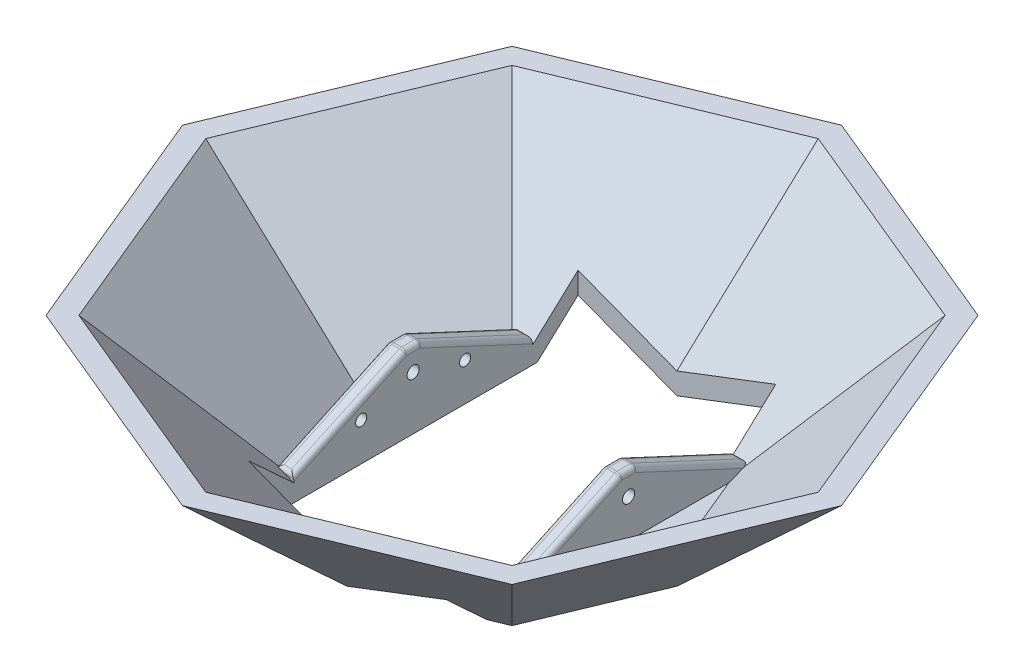
SolidWorks part; units mm, degrees
ref_plane "Ebene vorne" through (0, 0, 0) normal (0, 0, 1) x (1, 0, 0)
ref_plane "Ebene oben" through (0, 0, 0) normal (0, 1, 0) x (1, 0, 0)
ref_plane "Ebene rechts" through (0, 0, 0) normal (1, 0, 0) x (0, 0, -1)
sketch "Skizze1" plane through (0, 0, 0) normal (0, 1, 0) x (1, 0, 0)
  line L1 (-55, 0) -> (55, 0) construction
  line L5 (45.9619, -45.9619) -> (65, 0)
  line L6 (-65, 0) -> (65, 0) construction
  line L7 (0, -55) -> (0, 55) construction
  line L8 (0, 65) -> (0, -65) construction
  line L9 (0, -65) -> (45.9619, -45.9619)
  line L10 (45.9619, 45.9619) -> (-45.9619, -45.9619) construction
  line L11 (45.9619, -45.9619) -> (-45.9619, 45.9619) construction
  line L12 (-45.9619, -45.9619) -> (0, -65)
  line L15 (-65, 0) -> (-45.9619, -45.9619)
  line L16 (-45.9619, 45.9619) -> (-65, 0)
  line L19 (0, 65) -> (-45.9619, 45.9619)
  line L20 (45.9619, 45.9619) -> (0, 65)
  line L23 (65, 0) -> (45.9619, 45.9619)
  point P21 (0, 0)
  dimension "D1" = 45
  dimension "D2" = 130
  dimension "D5" = 4
extrude "Aufsatz-Linear austragen1" add sketch "Skizze1" along normal blind 30
ref_plane "Ebene1" through (26.8078, 0, 64.7198) normal (0.3827, 0, 0.9239) x (0.9239, 0, -0.3827)
ref_plane "Ebene3" through (-26.8078, 0, 64.7198) normal (-0.3827, 0, 0.9239) x (0.9239, 0, 0.3827)
ref_plane "Ebene4" through (-64.7198, 0, 26.8078) normal (-0.9239, 0, 0.3827) x (0.3827, 0, 0.9239)
ref_plane "Ebene5" through (-64.7198, 0, -26.8078) normal (-0.9239, 0, -0.3827) x (-0.3827, 0, 0.9239)
ref_plane "Ebene6" through (-26.8078, 0, -64.7198) normal (-0.3827, 0, -0.9239) x (-0.9239, 0, 0.3827)
sketch "Skizze6" plane through (-26.8078, 0, 64.7198) normal (-0.3827, 0, 0.9239) x (0.9239, 0, 0.3827)
  line L0 (-60.0522, 30) -> (-30.0522, 0)
  line L1 (-30.0522, 0) -> (-60.0522, 0)
  line L2 (71.5, 0) -> (-71.5, 0) construction
  line L3 (-60.0522, 0) -> (-60.0522, 30)
  line L4 (30.0522, 0) -> (60.0522, 30)
  line L5 (60.0522, 30) -> (60.0522, 0)
  line L6 (60.0522, 30) -> (60.0522, 0) construction
  line L7 (60.0522, 0) -> (30.0522, 0)
  dimension "D1" = 30
  dimension "D2" = 30
extrude "Schnitt-Linear austragen4" cut sketch "Skizze6" against normal through all
sketch "Skizze7" plane through (-64.7198, 0, 26.8078) normal (-0.9239, 0, 0.3827) x (0.3827, 0, 0.9239)
  line L0 (-60.0522, 30) -> (-30.0522, 0)
  line L1 (71.5, 0) -> (-71.5, 0) construction
  line L2 (-30.0522, 0) -> (-60.0522, 0)
  line L3 (-60.0522, 0) -> (-60.0522, 30) construction
  line L4 (-60.0522, 0) -> (-60.0522, 30)
  line L5 (30.0522, 0) -> (60.0522, 0)
  line L6 (24.8744, 0) -> (60.0522, 0) construction
  line L7 (60.0522, 30) -> (60.0522, 0) construction
  line L8 (60.0522, 0) -> (60.0522, 30)
  line L9 (60.0522, 30) -> (30.0522, 0)
  dimension "D1" = 30
  dimension "D2" = 30
extrude "Schnitt-Linear austragen5" cut sketch "Skizze7" against normal through all
sketch "Skizze8" plane through (-64.7198, 0, -26.8078) normal (-0.9239, 0, -0.3827) x (-0.3827, 0, 0.9239)
  line L0 (-60.0522, 30) -> (-60.0522, 0)
  line L1 (81.0088, 0) -> (-81.0088, 0) construction
  line L2 (-60.0522, 0) -> (-60.0522, 30) construction
  line L3 (-60.0522, 0) -> (-30.0522, 0)
  line L4 (-30.0522, 0) -> (-60.0522, 30)
  line L5 (60.0522, 30) -> (60.0522, 0)
  line L6 (60.0522, 0) -> (30.0522, 0)
  line L7 (54.8744, 0) -> (-12.448, 0) construction
  line L8 (30.0522, 0) -> (60.0522, 30)
  dimension "D1" = 30
  dimension "D2" = 30
extrude "Schnitt-Linear austragen6" cut sketch "Skizze8" against normal through all
sketch "Skizze9" plane through (-26.8078, 0, -64.7198) normal (-0.3827, 0, -0.9239) x (-0.9239, 0, 0.3827)
  line L0 (60.0522, 30) -> (60.0522, 0)
  line L1 (71.5, 0) -> (-71.5, 0) construction
  line L2 (60.0522, 0) -> (30.0522, 0)
  line L3 (30.0522, 0) -> (60.0522, 30)
  line L4 (-60.0522, 30) -> (-60.0522, 0)
  line L5 (-60.0522, 0) -> (-30.0522, 0)
  line L6 (-30.0522, 0) -> (-60.0522, 30)
  dimension "D1" = 30
  dimension "D2" = 30
extrude "Schnitt-Linear austragen7" cut sketch "Skizze9" against normal through all
shell "Wandung1" thickness 3 removed face at (0, 30, 0)
sketch "Skizze5" plane through (0, 0, 0) normal (0, -1, 0) x (1, 0, 0)
  line L6 (-19.5, -32.5282) -> (19.5, -32.5282)
  line L7 (-19.5, -32.5282) -> (-19.5, 32.5282)
  line L8 (-19.5, 32.5282) -> (19.5, 32.5282)
  line L9 (19.5, -32.5282) -> (19.5, 32.5282)
  line L10 (-19.5, -32.5282) -> (19.5, 32.5282) construction
  line L11 (-19.5, 32.5282) -> (19.5, -32.5282) construction
  point P0 (0, 0)
  dimension "D1" = 39
  dimension "D2" = 0
extrude "Schnitt-Linear austragen8" cut sketch "Skizze5" against normal through all
sketch "Skizze10" plane through (0, 3, 0) normal (0, 1, 0) x (1, 0, 0)
  line L0 (19.5, -23.106) -> (19.5, 23.106) construction
  line L1 (19.5, 23.5282) -> (23, 23.5282)
  line L2 (19.5, 23.5282) -> (19.5, -23.5282)
  line L3 (19.5, -23.5282) -> (23, -23.5282)
  line L4 (23, 23.5282) -> (23, -23.5282)
  line L5 (0, -32.5282) -> (19.5, -32.5282) construction
  line L6 (19.5, 32.5282) -> (0, 32.5282) construction
  line L7 (0, -16.5) -> (0, 16.5) construction
  line L8 (-19.5, -23.5282) -> (-23, -23.5282)
  line L9 (-23, 23.5282) -> (-23, -23.5282)
  line L10 (-19.5, 23.5282) -> (-23, 23.5282)
  line L11 (-19.5, 23.5282) -> (-19.5, -23.5282)
  dimension "D1" = 9
  dimension "D2" = 9
  dimension "D3" = 3.5
extrude "Aufsatz-Linear austragen2" add sketch "Skizze10" along normal blind 12
sketch "Skizze11" plane through (-23, 0, 0) normal (-1, 0, 0) x (0, 0, 1)
  line L0 (-23.5282, 15) -> (-23.5282, 4.7294)
  line L1 (-23.5282, 15) -> (-23.5282, 4.7294) construction
  line L2 (-23.5282, 4.7294) -> (-1.5282, 15)
  line L3 (-23.5282, 15) -> (23.5282, 15) construction
  line L4 (-1.5282, 15) -> (-23.5282, 15)
  line L5 (1.5282, 15) -> (23.5282, 15)
  line L6 (23.5282, 15) -> (23.5282, 4.7294)
  line L7 (23.5282, 4.7294) -> (1.5282, 15)
  dimension "D1" = 22
  dimension "D2" = 22
extrude "Schnitt-Linear austragen9" cut sketch "Skizze11" against normal blind 46
fillet "Verrundung1" radius 1 20 edges at (19.5, 9.8647, -12.5282) (21.25, 4.7294, -23.5282) (23, 9.8647, -12.5282) (23, 15, 0) (19.5, 15, 0) (21.25, 15, -1.5282) (19.5, 9.8647, 12.5282) (21.25, 15, 1.5282) (23, 9.8647, 12.5282) (21.25, 4.7294, 23.5282) (-19.5, 9.8647, -12.5282) (-23, 9.8647, -12.5282) (-21.25, 4.7294, -23.5282) (-23, 15, 0) (-21.25, 15, -1.5282) (-19.5, 15, 0) (-19.5, 9.8647, 12.5282) (-21.25, 4.7294, 23.5282) (-23, 9.8647, 12.5282) (-21.25, 15, 1.5282)
sketch "Skizze12" plane through (-23, 0, 0) normal (-1, 0, 0) x (0, 0, 1)
  line L0 (0, 0) -> (0, 30) construction
  circle A0 centre (0, 10.5496) radius 1.2
  dimension "D1" = 2.4
extrude "Schnitt-Linear austragen10" cut sketch "Skizze12" against normal blind 46
sketch "Skizze13" plane through (-23, 0, 0) normal (-1, 0, 0) x (0, 0, 1)
  line L0 (0, 0) -> (0, 30) construction
  line L1 (-19.756, 3) -> (19.756, 3) construction
  line L2 (0, -16.5) -> (0, 16.5) construction
  circle A0 centre (10.25, 7.5) radius 1.1
  circle A1 centre (-10.25, 7.5) radius 1.1
  dimension "D1" = 10.25
  dimension "D2" = 4.5
  dimension "D3" = 2.2
extrude "Schnitt-Linear austragen11" cut sketch "Skizze13" against normal blind 16
